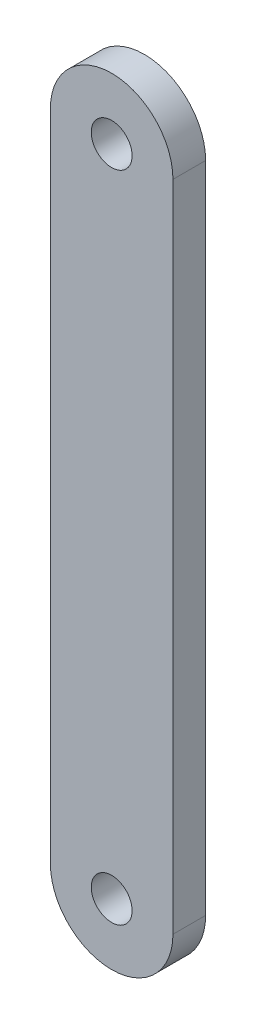
SolidWorks part; units mm, degrees
ref_plane "Front Plane" through (0, 0, 0) normal (0, 0, 1) x (1, 0, 0)
ref_plane "Top Plane" through (0, 0, 0) normal (0, 1, 0) x (1, 0, 0)
ref_plane "Right Plane" through (0, 0, 0) normal (1, 0, 0) x (0, 0, -1)
sketch "Sketch1" plane through (0, 0, 0) normal (0, 0, 1) x (1, 0, 0)
  line L0 (0, -25.4) -> (0, 25.4) construction
  line L1 (-4.7625, -25.4) -> (-4.7625, 25.4)
  line L2 (4.7625, -25.4) -> (4.7625, 25.4)
  arc A0 (-4.7625, -25.4) -> (4.7625, -25.4) centre (0, -25.4) ccw
  arc A1 (4.7625, 25.4) -> (-4.7625, 25.4) centre (0, 25.4) ccw
  circle A2 centre (0, 25.4) radius 1.5875
  circle A3 centre (0, -25.4) radius 1.5875
  point P3 (0, 0)
  dimension "D2" = 4.7625
  dimension "D3" = 3.175
  dimension "D1" = 50.8
extrude "Boss-Extrude1" add sketch "Sketch1" along normal blind 2.54
ref_axis "Axis1" through (0, -25.4, 2.54) along (0, 0, -1)
ref_axis "Axis2" through (0, 25.4, 2.54) along (0, 0, -1)
